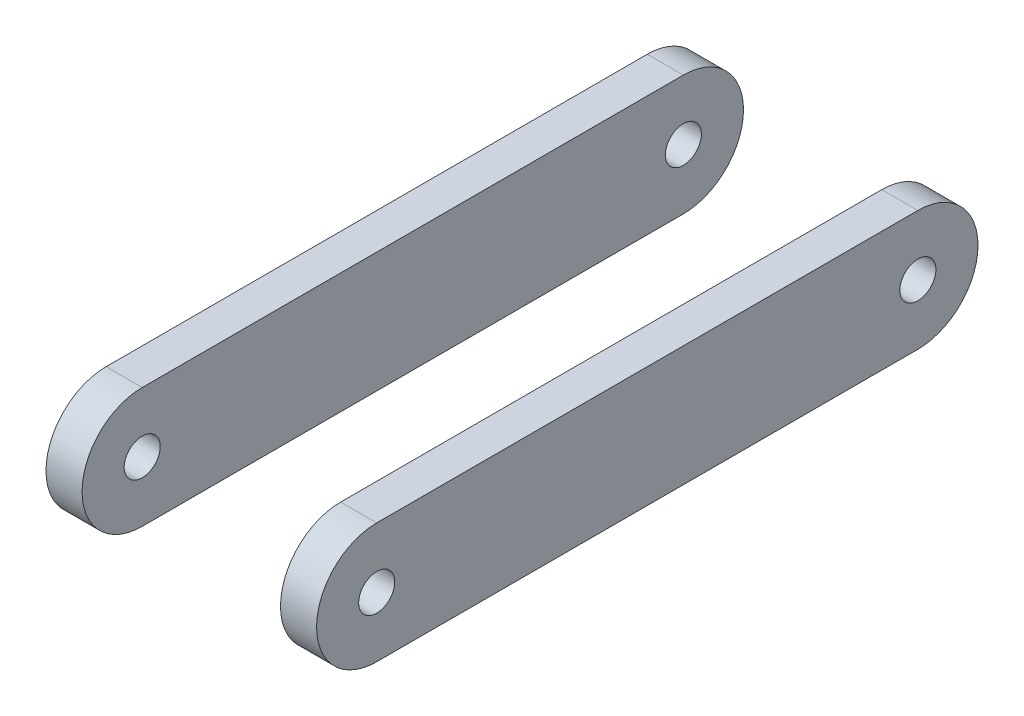
SolidWorks part; units mm, degrees
ref_plane "Front Plane" through (0, 0, 0) normal (0, 0, 1) x (1, 0, 0)
ref_plane "Top Plane" through (0, 0, 0) normal (0, 1, 0) x (1, 0, 0)
ref_plane "Right Plane" through (0, 0, 0) normal (1, 0, 0) x (0, 0, -1)
sketch "length (ref to equation file)" plane through (0, 0, 0) normal (1, 0, 0) x (0, 0, -1)
  line L0 (0, 0) -> (90, 0)
  dimension "D1" = 90
ref_axis "pivot w/ link 1" through (0, 0, 0) along (1, 0, 0)
ref_axis "pivot w/ platform" through (0, 0, -90) along (1, 0, 0)
ref_plane "Plane1" through (16.5, 0, 0) normal (1, 0, 0) x (0, 0, -1)
sketch "Sketch1" plane through (16.5, 0, 0) normal (1, 0, 0) x (0, 0, -1)
  line L0 (0, 0) -> (90, 0) construction
  line L1 (0, 10) -> (90, 10)
  line L2 (0, -10) -> (90, -10)
  arc A0 (0, 10) -> (0, -10) centre (0, 0) ccw
  arc A1 (90, -10) -> (90, 10) centre (90, 0) ccw
  point P4 (45, 0)
  dimension "D1" = 20
extrude "Boss-Extrude1" add sketch "Sketch1" along normal blind 6 contours L2 A1 L1 A0
sketch "Sketch2" plane through (22.5, 0, 0) normal (1, 0, 0) x (0, 0, -1)
  circle A0 centre (0, 0) radius 3
  circle A1 centre (0, 0) radius 3 construction
  circle A2 centre (90, 0) radius 3
extrude "Cut-Extrude1" cut sketch "Sketch2" against normal through all and the other way through all
mirror "Mirror4" about plane through (0, 0, 0) normal (1, 0, 0) of bodies 103
equation "\"link 2\"= 90mm"
equation "\"D1@length (ref to equation file)\" = \"link 2\""
equation "\"link 1 thickness\" = 6mm"
equation "\"beam width\" = 27mm"
equation "\"beam side wall thickness\" = 3mm"
equation "\"D1@Plane1\" = \"link 2 plane\""
equation "\"link 2 plane\"= \"beam side wall thickness\" + \"beam width\" / 2"
equation "\"motor center z\" = 60mm"
equation "\"motor center y\" = 20mm"
equation "\"link 1\" = 40mm"
equation "\"pivot height\"= 140mm"
equation "\"beam length\" = 120mm"
equation "\"camera height\" = 250mm"
equation "\"link height\" = 20mm"
equation "\"D1@Sketch1\"=\"link height\""
equation "\"D1@Boss-Extrude1\"=\"link 1 thickness\""
